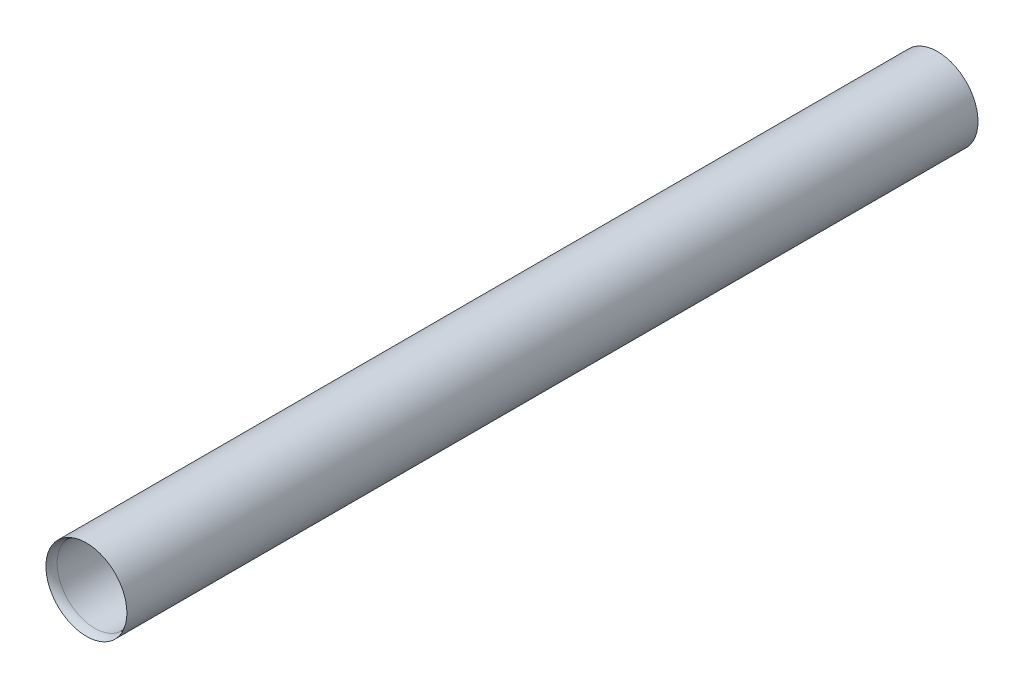
SolidWorks part; units mm, degrees
ref_plane "Front Plane" through (0, 0, 0) normal (0, 0, 1) x (1, 0, 0)
ref_plane "Top Plane" through (0, 0, 0) normal (0, 1, 0) x (1, 0, 0)
ref_plane "Right Plane" through (0, 0, 0) normal (1, 0, 0) x (0, 0, -1)
sketch "Sketch1" plane through (0, 0, 0) normal (0, 0, 1) x (1, 0, 0)
  circle A0 centre (0, 0) radius 14.5
  dimension "D1" = 29
extrude "Boss-Extrude1" add sketch "Sketch1" against normal blind 304.8
sketch "Sketch2" plane through (0, 0, 0) normal (0, 0, 1) x (1, 0, 0)
  circle A0 centre (0, 0) radius 13.5
  circle A1 centre (0, 0) radius 14.5 construction
  dimension "D1" = 1
extrude "Cut-Extrude1" cut sketch "Sketch2" against normal blind 304.8
fillet "Fillet3" radius 5 1 edges at (13.5, 0, 0)
